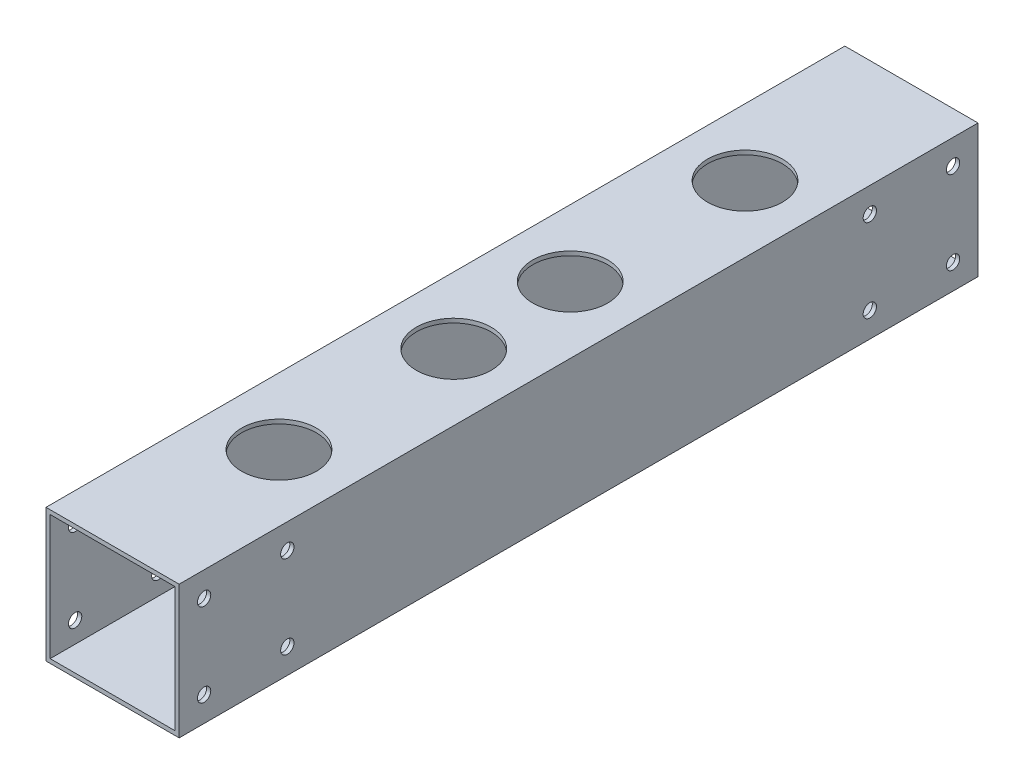
SolidWorks part; units mm, degrees
material "1060 Alloy"
ref_plane "Front Plane" through (0, 0, 0) normal (0, 0, 1) x (1, 0, 0)
ref_plane "Top Plane" through (0, 0, 0) normal (0, 1, 0) x (1, 0, 0)
ref_plane "Right Plane" through (0, 0, 0) normal (1, 0, 0) x (0, 0, -1)
sketch "Sketch2" plane through (0, 0, 0) normal (0, 0, 1) x (1, 0, 0)
  line L1 (-25.4, -25.4) -> (25.4, -25.4)
  line L2 (-25.4, -25.4) -> (-25.4, 25.4)
  line L3 (-25.4, 25.4) -> (25.4, 25.4)
  line L4 (25.4, -25.4) -> (25.4, 25.4)
  line L5 (-23.8125, -23.8125) -> (23.8125, -23.8125)
  line L6 (-23.8125, -23.8125) -> (-23.8125, 23.8125)
  line L7 (-23.8125, 23.8125) -> (23.8125, 23.8125)
  line L8 (23.8125, -23.8125) -> (23.8125, 23.8125)
  point P11 (0, -23.8125)
  point P13 (-23.8125, 0)
  dimension "D1" = 50.8
  dimension "D2" = 50.8
  dimension "D3" = 1.5875
  dimension "D4" = 1.5875
  dimension "D5" = 1.5875
  dimension "D6" = 1.5875
extrude "Boss-Extrude1" add sketch "Sketch2" along normal mid plane 304.8
sketch "Sketch3" plane through (0, 25.4, 0) normal (0, 1, 0) x (1, 0, 0)
  line L0 (-25.4, 0) -> (25.4, 0) construction
  line L1 (-25.4, -152.4) -> (-25.4, 152.4) construction
  line L2 (25.4, -152.4) -> (25.4, 152.4) construction
  circle A0 centre (0, -88.9) radius 14.2875
  circle A3 centre (0, -22.225) radius 14.2875
  circle A4 centre (0, 22.225) radius 14.2875
  circle A5 centre (0, 88.9) radius 14.2875
  dimension "D1" = 28.575
  dimension "D2" = 25.4
  dimension "D3" = 88.9
  dimension "D4" = 22.225
extrude "Cut-Extrude1" cut sketch "Sketch3" against normal through all
sketch "Sketch4" plane through (-25.4, 0, 0) normal (-1, 0, 0) x (0, 0, 1)
  line L0 (0, 25.4) -> (0, -25.4) construction
  line L1 (152.4, 25.4) -> (-152.4, 25.4) construction
  line L2 (152.4, -25.4) -> (-152.4, -25.4) construction
  line L3 (-101.6, 25.4) -> (-101.6, -25.4) construction
  line L4 (-152.4, 25.4) -> (-152.4, -25.4) construction
  circle A0 centre (-142.875, 15.875) radius 2.54
  circle A1 centre (-142.875, -15.875) radius 2.54
  circle A2 centre (-111.125, 15.875) radius 2.54
  circle A3 centre (-111.125, -15.875) radius 2.54
  circle A4 centre (111.125, -15.875) radius 2.54
  circle A5 centre (111.125, 15.875) radius 2.54
  circle A6 centre (142.875, -15.875) radius 2.54
  circle A7 centre (142.875, 15.875) radius 2.54
  dimension "D2" = 5.08
  dimension "D1" = 50.8
  dimension "D3" = 9.525
  dimension "D4" = 9.525
  dimension "D5" = 9.525
  dimension "D6" = 9.525
extrude "Cut-Extrude2" cut sketch "Sketch4" against normal through all both and the other way through all
